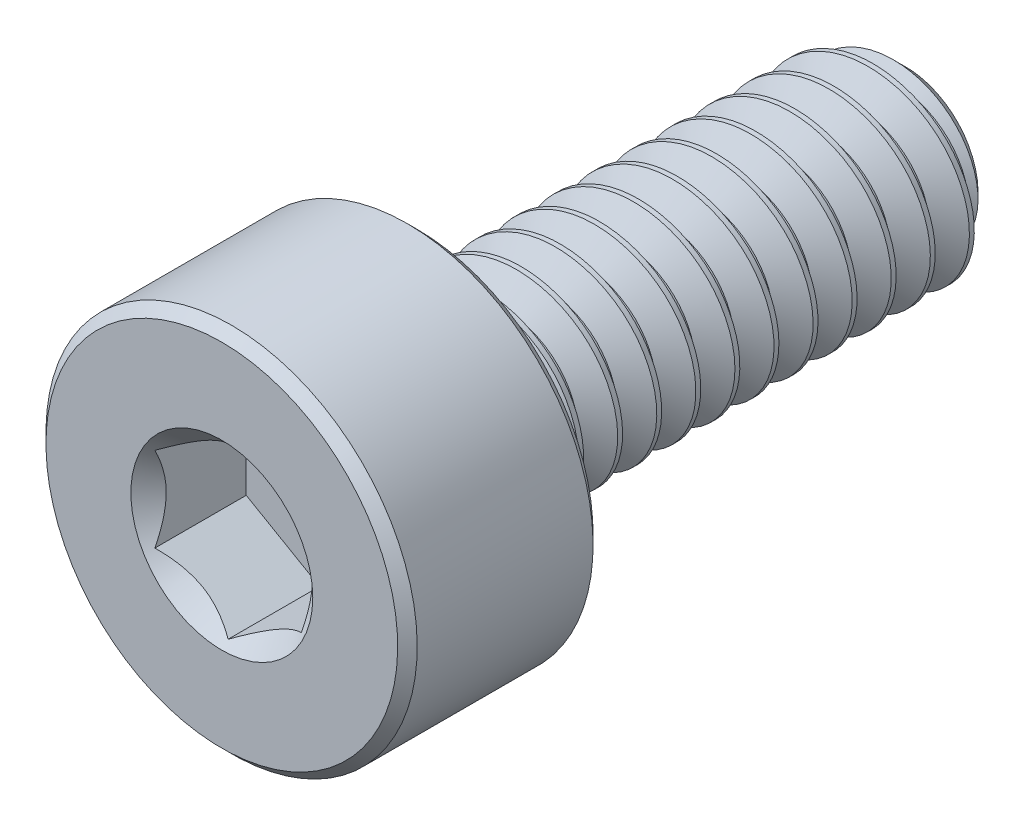
SolidWorks part; units mm, degrees
ref_plane "Front Plane" through (0, 0, 0) normal (0, 0, 1) x (1, 0, 0)
ref_plane "Top Plane" through (0, 0, 0) normal (0, 1, 0) x (1, 0, 0)
ref_plane "Right Plane" through (0, 0, 0) normal (1, 0, 0) x (0, 0, -1)
sketch "Sketch1" plane through (0, 0, 0) normal (1, 0, 0) x (0, 0, -1)
  line L0 (-3.5, 0) -> (3.5, 0) construction
  line L1 (3.5, 0) -> (3.5, 0.7402) construction
  line L2 (3.5, 0.7402) -> (3.2402, 1) construction
  line L3 (3.2402, 1) -> (3.2, 1) construction
  line L4 (3.2, 1) -> (-1.5, 1) construction
  line L5 (-1.5, 1) -> (-1.5, 1.9) construction
  line L6 (-1.5, 1.9) -> (-3.5, 1.9) construction
  line L7 (-3.5, 1.9) -> (-3.5, 0) construction
  line L8 (3.5, 0.7402) -> (3.5, 1) construction
  line L9 (3.475, 1.0433) -> (3.675, 0.6969) construction
  line L10 (3.675, 0.6969) -> (3.875, 1.0433) construction
  line L11 (3.875, 1.0433) -> (3.475, 1.0433) construction
  line L12 (3.675, 1.0433) -> (3.675, 1) construction
  line L13 (3.675, 0.6969) -> (3.675, 0.7402) construction
  line L14 (3.65, 0.7402) -> (3.7, 0.7402) construction
  line L15 (3.5, 1) -> (3.85, 1) construction
  line L16 (3.4875, 1.0217) -> (3.8625, 1.0217) construction
  line L17 (3.5, 0) -> (3.5, -1) construction
  line L18 (-1.6, 1.9) -> (-1.5, 1.8) construction
  line L19 (-3.4, 1.9) -> (-3.5, 1.8) construction
  line L20 (-1.5, 1) -> (-1.5, 0) construction
  line L21 (-1.5, 0.5) -> (0.1667, 0.5) construction
  line L22 (0.1667, 0.5) -> (1.8333, 0.5) construction
  line L23 (1.8333, 0.5) -> (3.5, 0.5) construction
  line L24 (0.1667, 0.5) -> (0.1667, 1) construction
  line L25 (0.1667, 1) -> (0.1667, 1.9) construction
  line L26 (1.8333, 0.5) -> (1.8333, 1.9) construction
  point P0 (-3.5, 0.75)
  point P3 (2.5, 1)
  point P4 (0, 0)
  point P18 (1.8333, 1)
  point P22 (3.675, 0.7402)
  point P24 (3.2, 1)
  point P25 (3.675, 1)
  point P28 (3.675, 1.0217)
  point P29 (2.5, -1)
  point P30 (0.1667, 1)
  point P31 (-2.5, 1.9)
  point P37 (-1.85, 1.9)
  point P38 (-3.35, 1.9)
  point P45 (0.1667, 0.5)
  point P46 (1.8333, 0.5)
  dimension "D2" = 0.05
  dimension "D7" = 0.1
  dimension "D8" = 0.1
  dimension "D9" = 0.1
  dimension "D10" = 0.05
  dimension "D11" = 0.25
  dimension "Drive Size" = 1.5
  dimension "Head Diameter" = 3.8
  dimension "Head Height" = 2
  dimension "Thread Pitch" = 0.4
  dimension "Thread Dia" = 2
  dimension "Length" = 5
  dimension "D12" = 0.3
  dimension "D4" = 1
  dimension "D3" = 45
sketch "Sketch2" plane through (0, 0, 0) normal (1, 0, 0) x (0, 0, -1)
  line L0 (-3.5, 0) -> (-3.5, 1.8)
  line L1 (-3.4, 1.9) -> (-1.6, 1.9)
  line L2 (-1.5, 1.8) -> (-1.5, 1.1)
  line L4 (3.2402, 1) -> (3.5, 0.7402)
  line L5 (3.5, 0.7402) -> (3.5, 0)
  line L6 (-1.5, 1.9) -> (-3.5, 1.9) construction
  line L7 (3.5, 0) -> (-3.5, 0)
  line L8 (-3.4, 1.9) -> (-3.5, 1.8) construction
  line L10 (-3.4, 1.9) -> (-3.5, 1.8)
  line L14 (-1.6, 1.9) -> (-1.5, 1.8) construction
  line L16 (-1.6, 1.9) -> (-1.5, 1.8)
  line L17 (-1.5, 1) -> (-1.5, 1.9) construction
  line L19 (-1.4, 1) -> (3.2402, 1)
  line L20 (3.2, 1) -> (-1.5, 1) construction
  arc A1 (-1.5, 1.1) -> (-1.4, 1) centre (-1.4, 1.1) ccw
  dimension "D3" = 0.1
revolve "Revolve1" add sketch "Sketch2" angle 360 about L7
sketch "Sketch3" plane through (0, 0, 3.5) normal (0, 0, 1) x (1, 0, 0)
  line L1 (0.75, -0.433) -> (0.75, 0.433)
  line L2 (0.75, 0.433) -> (0, 0.866)
  line L3 (0, 0.866) -> (-0.75, 0.433)
  line L4 (-0.75, 0.433) -> (-0.75, -0.433)
  line L5 (-0.75, -0.433) -> (0, -0.866)
  line L6 (0, -0.866) -> (0.75, -0.433)
  circle A0 centre (0, 0) radius 0.75 construction
  circle A1 centre (0, 0) radius 1.9 construction
  circle A2 centre (0, 0) radius 1.9 construction
  circle A3 centre (0, 0) radius 0.866 construction
  point P13 (0, 0)
  dimension "D1" = 1.7321
extrude "Cut-Extrude1" cut sketch "Sketch3" against normal offset from surface (1 mm away) 1 up to face at (0, 1.8, 1.5)
sketch "Sketch4" plane through (0, 0, 3.5) normal (0, 0, 1) x (1, 0, 0)
  circle A0 centre (0, 0) radius 0.931
  dimension "D1" = 1.862
extrude "Cut-Extrude2" cut sketch "Sketch4" against normal up to vertex (1 mm away) draft 45 up to point (0, 1.9, 2.5)
sketch "Sketch11" plane through (0, 0, 0) normal (1, 0, 0) x (0, 0, -1)
  line L0 (-3.5, 0) -> (3.5, 0) construction
  line L1 (-3.5, 0) -> (3.5, 0) construction
  line L2 (-0.5625, 0) -> (-0.5625, 1) construction
  line L3 (3.2, 1) -> (-1.5, 1) construction
  line L4 (2.5625, 0) -> (2.5625, 1) construction
  line L6 (3.5, 0.7402) -> (3.5, 1) construction
  point P2 (-0.5625, 0)
  point P3 (2.5625, 0)
  dimension "D1" = 0.9375
  dimension "D2" = 0.9375
sketch "Sketch6" plane through (0, 0, -3.5) normal (0, 0, -1) x (-1, 0, 0)
  circle A0 centre (0, 0) radius 1
curve "Helix/Spiral1" pitch 0.4 height 5.4 turns 13.5
sketch "Sketch10" plane through (0, 0, 0) normal (1, 0, 0) x (0, 0, -1)
  line L0 (-1.4, -1.9) -> (-1.4, 1.9)
  line L5 (-3.5, 0) -> (3.5, 0) construction
  line L6 (-1.4, 1) -> (-1.4, -1) construction
  point P3 (-1.4, 0)
split "Split1" trim tools "Sketch10" bodies to split 106 resulting bodies 114 115
sketch "Sketch7" plane through (0, 0, 0) normal (1, 0, 0) x (0, 0, -1)
  line L0 (3.4875, 1.0217) -> (3.8625, 1.0217)
  line L1 (3.8625, 1.0217) -> (3.7, 0.7402)
  line L2 (3.7, 0.7402) -> (3.65, 0.7402)
  line L3 (3.65, 0.7402) -> (3.4875, 1.0217)
sweep "Cut-Sweep1" cut profiles "Sketch7" path "Helix/Spiral1" align with end faces yes
sketch "Sketch8" plane through (0, 0, 0) normal (1, 0, 0) x (0, 0, -1)
  line L0 (-1.5, 0) -> (-1.5, 1)
  line L1 (-1.4, -1) -> (-1.4, 1) construction
  line L2 (-1.5, 1) -> (-1.4, 1)
  line L4 (-1.4, 1) -> (-0.8226, 0)
  line L5 (-0.8226, 0) -> (-1.5, 0)
  line L6 (3.2, 1) -> (-1.5, 1) construction
  line L7 (-3.5, 0) -> (3.5, 0) construction
  dimension "D1" = 60
revolve "Revolve2" add sketch "Sketch8" angle 360 about L5
equation "\"D2@Sketch1\" = \"Thread Pitch@Sketch1\" / 8"
equation "\"D4@Helix/Spiral1\" = \"Thread Pitch@Sketch1\""
equation "\"D7@Sketch1\" = \"Head Height@Sketch1\" * .05"
equation "\"D8@Sketch1\"=\"D7@Sketch1\""
equation "\"D9@Sketch1\"=\"D7@Sketch1\""
equation "\"D10@Sketch1\"=\"D7@Sketch1\"/2"
equation "\"D11@Sketch1\"=\"D10@Sketch1\"*5"
equation "\"D4@Sketch1\"=\"Thread Pitch@Sketch1\"*2.5"
equation "\"D12@Sketch1\"=\"Thread Pitch@Sketch1\"*.75"
equation "\"D3@Helix/Spiral1\"=\"Length@Sketch1\"+\"Thread Pitch@Sketch1\""
equation "\"D3@Sketch2\"=\"Thread Dia@Sketch1\"*0.05"
equation "\"D1@Sketch11\"=\"Length@Sketch1\"*0.1875"
equation "\"D2@Sketch11\"=\"D1@Sketch11\""
equation "\"D1@Sketch4\"=\"D1@Sketch3\"*1.075"
